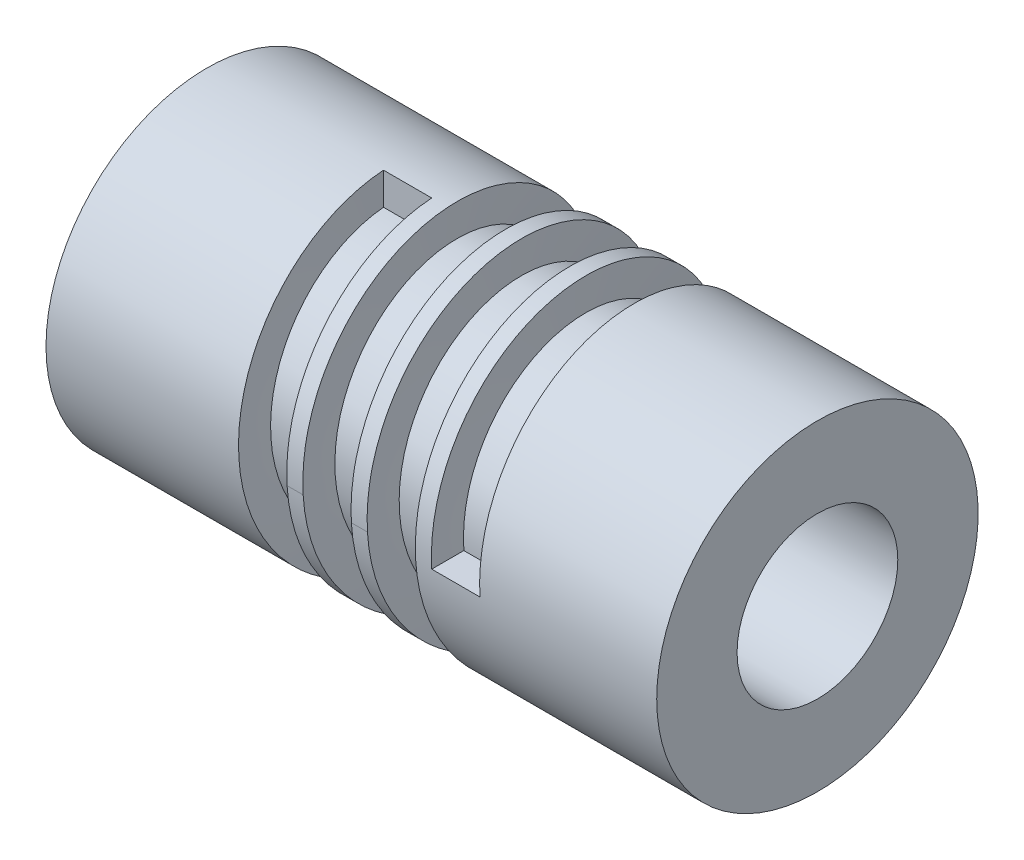
SolidWorks part; units mm, degrees
ref_plane "Front Plane" through (0, 0, 0) normal (0, 0, 1) x (1, 0, 0)
ref_plane "Top Plane" through (0, 0, 0) normal (0, 1, 0) x (1, 0, 0)
ref_plane "Right Plane" through (0, 0, 0) normal (1, 0, 0) x (0, 0, -1)
sketch "Sketch1" plane through (0, 0, 0) normal (0, 0, 1) x (1, 0, 0)
  line L0 (-30.5045, 0) -> (69.1048, 0) construction
  line L1 (7.4955, 5) -> (7.4955, 10)
  line L2 (7.4955, 10) -> (-30.5045, 10)
  line L3 (-30.5045, 10) -> (-30.5045, 2.5)
  line L4 (-30.5045, 2.5) -> (-20.5045, 2.5)
  line L5 (-20.5045, 2.5) -> (-20.5045, 0)
  line L6 (-20.5045, 0) -> (-2.5045, 0)
  line L7 (-2.5045, 0) -> (-2.5045, 5)
  line L8 (-2.5045, 5) -> (7.4955, 5)
  dimension "D1" = 5
  dimension "D2" = 2.5
  dimension "D3" = 10
  dimension "D4" = 10
  dimension "D5" = 10
  dimension "D6" = 38
revolve "Revolve1" add sketch "Sketch1" angle 360 about L0
sketch "Sketch2" plane through (0, 0, 0) normal (0, 0, 1) x (1, 0, 0)
  line L0 (7.4955, 10) -> (-30.5045, 10) construction
  line L1 (-7.5045, 10) -> (-4.5045, 10)
  line L2 (-7.5045, 10) -> (-7.5045, 8)
  line L3 (-7.5045, 8) -> (-4.5045, 8)
  line L4 (-4.5045, 10) -> (-4.5045, 8)
  dimension "D1" = 3
  dimension "D2" = 2
  dimension "D3" = 2
ref_plane "Plane1" through (-14, 0, 0) normal (1, 0, 0) x (0, 0, -1)
sketch "Sketch4" plane through (-14, 0, 0) normal (1, 0, 0) x (0, 0, -1)
  circle A0 centre (0, 0) radius 10
  dimension "D1" = 20
curve "Helix/Spiral1" pitch 4 height 13 turns 3.25
sweep "Cut-Sweep1" cut profiles "Sketch2" path "Helix/Spiral1"
